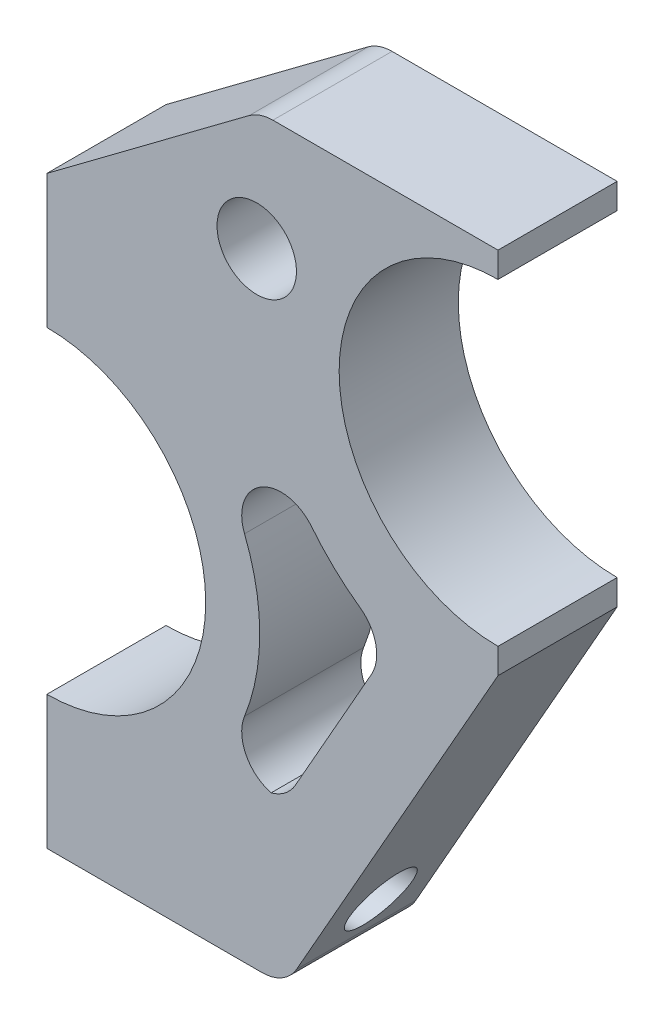
SolidWorks part; units mm, degrees
material "Plain Carbon Steel"
ref_plane "Front Plane" through (0, 0, 0) normal (0, 0, 1) x (1, 0, 0)
ref_plane "Top Plane" through (0, 0, 0) normal (0, 1, 0) x (1, 0, 0)
ref_plane "Right Plane" through (0, 0, 0) normal (1, 0, 0) x (0, 0, -1)
sketch "Sketch1" plane through (0, 0, 0) normal (0, 0, 1) x (1, 0, 0)
  line L0 (-150.9322, 816.6511) -> (-142.4093, 831.6717)
  line L10 (-156.6282, 837.9871) -> (-149.5887, 837.9871)
  line L11 (-156.3603, 807.0849) -> (-139.3423, 837.0769) construction
  line L12 (-156.6282, 816.6511) -> (-150.9322, 816.6511)
  line L16 (-169.8874, 850.6871) -> (-169.8874, 837.9871)
  line L17 (-152.8694, 863.4071) -> (-169.8874, 850.6871)
  line L18 (-133.8194, 863.4071) -> (-152.8694, 863.4071)
  line L19 (-133.8194, 861.3751) -> (-133.8194, 863.4071)
  line L20 (-133.8194, 833.9431) -> (-133.8194, 835.9751)
  line L21 (-150.8374, 803.9511) -> (-133.8194, 833.9431)
  line L22 (-169.8874, 803.9511) -> (-150.8374, 803.9511)
  line L23 (-169.8874, 816.6511) -> (-169.8874, 803.9511)
  line L24 (-169.8874, 850.6871) -> (-169.8874, 837.9871)
  line L25 (-152.8694, 863.4071) -> (-169.8874, 850.6871)
  line L26 (-133.8194, 863.4071) -> (-152.8694, 863.4071)
  line L27 (-133.8194, 861.3751) -> (-133.8194, 863.4071)
  line L28 (-133.8194, 833.9431) -> (-133.8194, 835.9751)
  line L29 (-150.8374, 803.9511) -> (-133.8194, 833.9431)
  line L30 (-169.8874, 803.9511) -> (-150.8374, 803.9511)
  line L31 (-169.8874, 816.6511) -> (-169.8874, 803.9511)
  arc A2 (-156.6282, 816.6511) -> (-156.6282, 837.9871) centre (-169.8874, 827.3191) ccw
  circle A3 centre (-153.1085, 853.8621) radius 3.175
  arc A6 (-169.8874, 810.3011) -> (-169.8874, 844.3371) centre (-169.8874, 827.3191) ccw construction
  arc A7 (-169.8874, 816.6511) -> (-169.8874, 837.9871) centre (-169.8874, 827.3191) ccw
  arc A8 (-133.8194, 861.3751) -> (-133.8194, 835.9751) centre (-133.8194, 848.6751) ccw
  arc A9 (-169.8874, 816.6511) -> (-169.8874, 837.9871) centre (-169.8874, 827.3191) ccw
  arc A10 (-133.8194, 861.3751) -> (-133.8194, 835.9751) centre (-133.8194, 848.6751) ccw
  arc A11 (-149.5887, 837.9871) -> (-142.4093, 831.6717) centre (-133.8194, 848.6751) ccw
  point P22 (-153.1085, 837.9871)
  dimension "D4" = 19.05
  dimension "D5" = 6.35
  dimension "D1" = 0
  dimension "D2" = 6.35
  dimension "D3" = 6.35
  dimension "D6" = 3.175
extrude "Boss-Extrude1" add sketch "Sketch1" along normal blind 9.525
sketch "Sketch3" plane through (-169.8874, 0, 0) normal (-1, 0, 0) x (0, 0, 1)
  line L0 (4.7625, 850.6871) -> (4.7625, 803.9511) construction
  line L1 (9.525, 850.6871) -> (0, 850.6871) construction
  line L2 (9.525, 803.9511) -> (0, 803.9511) construction
  circle A0 centre (4.7625, 845.6071) radius 2.54
  circle A1 centre (4.7625, 809.0311) radius 2.54
  dimension "D1" = 5.08
  dimension "D2" = 5.08
  dimension "D3" = 5.08
extrude "Cut-Extrude1" cut sketch "Sketch3" against normal blind 12.7
sketch "Sketch4" plane through (-157.1874, 0, 0) normal (-1, 0, 0) x (0, 0, 1)
  circle A0 centre (4.7625, 809.0311) radius 2.54 construction
  circle A1 centre (4.7625, 809.0311) radius 2.54
extrude "Cut-Extrude2" cut sketch "Sketch4" against normal up to next
fillet "Fillet1" radius 3.175 7 edges at (-152.8694, 863.4071, 4.7625) (-150.8374, 803.9511, 4.7625) (-150.9322, 816.6511, 4.7625) (-149.5887, 837.9871, 4.7625) (-156.6282, 837.9871, 4.7625) (-156.6282, 816.6511, 4.7625) (-142.4093, 831.6717, 4.7625)
sketch "Sketch5" plane through (0, 0, 0) normal (0, 0, -1) x (-1, 0, 0)
  circle A0 centre (169.8874, 827.3191) radius 12.7
  dimension "D1" = 25.4
extrude "Cut-Extrude3" cut sketch "Sketch5" against normal through all
